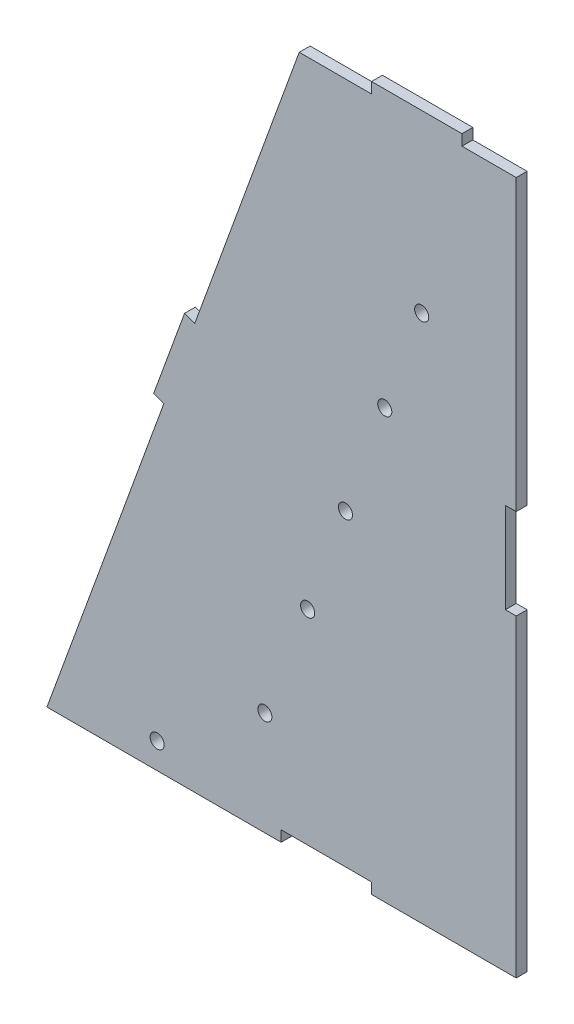
SolidWorks part; units mm, degrees
ref_plane "Спереди" through (0, 0, 0) normal (0, 0, 1) x (1, 0, 0)
ref_plane "Сверху" through (0, 0, 0) normal (0, 1, 0) x (1, 0, 0)
ref_plane "Справа" through (0, 0, 0) normal (1, 0, 0) x (0, 0, -1)
sketch "Эскиз1" plane through (0, 0, 0) normal (0, 0, 1) x (1, 0, 0)
  line L0 (-38.4665, 0) -> (26.3056, 0)
  line L1 (91.3056, 0) -> (91.3056, 86.6973)
  line L2 (91.3056, 191.6973) -> (76.3056, 191.6973)
  line L3 (31.3056, 191.6973) -> (2.4049, 112.2933)
  line L4 (2.4049, 112.2933) -> (-0.4142, 113.3193)
  line L5 (-0.4142, 113.3193) -> (-8.9647, 89.827)
  line L6 (-8.9647, 89.827) -> (-6.1456, 88.801)
  line L7 (-6.1456, 88.801) -> (-38.4665, 0)
  line L8 (91.3056, 111.6973) -> (88.3056, 111.6973)
  line L9 (88.3056, 111.6973) -> (88.3056, 86.6973)
  line L10 (88.3056, 86.6973) -> (91.3056, 86.6973)
  line L11 (51.3056, 0) -> (91.3056, 0)
  line L13 (26.3056, 0) -> (26.3056, 3)
  line L14 (26.3056, 3) -> (51.3056, 3)
  line L15 (51.3056, 0) -> (51.3056, 3)
  line L16 (91.3056, 111.6973) -> (91.3056, 191.6973)
  line L17 (51.3056, 191.6973) -> (31.3056, 191.6973)
  line L19 (51.3056, 191.6973) -> (51.3056, 194.6973)
  line L20 (51.3056, 194.6973) -> (76.3056, 194.6973)
  line L21 (76.3056, 191.6973) -> (76.3056, 194.6973)
  dimension "D1" = 70
  dimension "D2" = 70
  dimension "D3" = 25
  dimension "D4" = 204
  dimension "D5" = 84.5
  dimension "D6" = 3
  dimension "D7" = 60
  dimension "D8" = 129.7721
  dimension "D9" = 191.6973
  dimension "D10" = 25
  dimension "D11" = 3
  dimension "D12" = 80
  dimension "D13" = 25
  dimension "D14" = 3
  dimension "D15" = 40
  dimension "D16" = 25
  dimension "D17" = 3
  dimension "D18" = 15
extrude "Бобышка-Вытянуть1" add sketch "Эскиз1" along normal blind 3
sketch "Эскиз2" plane through (0, 0, 3) normal (0, 0, 1) x (1, 0, 0)
  line L7 (21.8002, 28.7042) -> (21.9526, 28.6481)
  circle A0 centre (65.1723, 146.157) radius 1.95
  circle A1 centre (54.9521, 118.3697) radius 1.95
  circle A2 centre (44.0831, 88.215) radius 1.95
  circle A3 centre (33.624, 59.4786) radius 1.95
  circle A4 centre (21.8002, 28.7042) radius 1.95
  circle A5 centre (-7.9882, 7.1347) radius 1.95
  point P26 (21.8002, 28.6481)
  dimension "D1" = 3.9
  dimension "D2" = 3.9
  dimension "D3" = 3.9
  dimension "D4" = 3.9
  dimension "D5" = 3.9
  dimension "D6" = 3.9
extrude "Вырез-Вытянуть1" cut sketch "Эскиз2" against normal through all contours A5 | A4 | A3 | A2 | A1 | A0 region at (54.9521, 118.3697, 3) region at (44.0831, 88.215, 3) region at (33.624, 59.4786, 3) region at (19.9053, 28.7042, 3) region at (-7.9882, 7.1347, 3)
